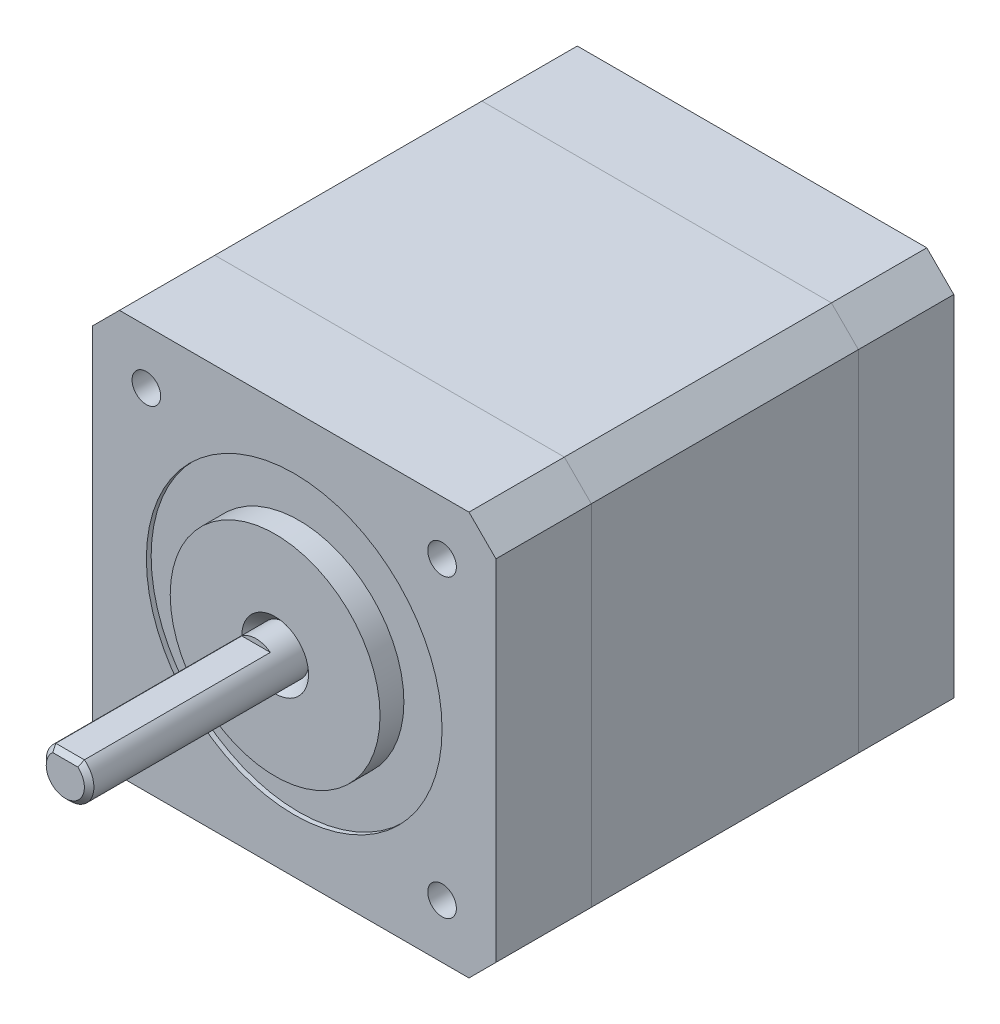
SolidWorks part; units mm, degrees
ref_plane "前视基准面" through (0, 0, 0) normal (0, 0, 1) x (1, 0, 0)
ref_plane "上视基准面" through (0, 0, 0) normal (0, 1, 0) x (1, 0, 0)
ref_plane "右视基准面" through (0, 0, 0) normal (1, 0, 0) x (0, 0, -1)
sketch "草图1" plane through (0, 0, 0) normal (0, 0, 1) x (1, 0, 0)
  line L0 (0, -21.15) -> (0, 21.15) construction
  line L1 (18.3216, 21.15) -> (-18.3216, 21.15)
  line L2 (-18.3216, 21.15) -> (-21.15, 18.3216)
  line L3 (-21.15, 18.3216) -> (-21.15, -18.3216)
  line L4 (-21.15, -18.3216) -> (-18.3216, -21.15)
  line L5 (-18.3216, -21.15) -> (18.3216, -21.15)
  line L6 (21.15, -18.3216) -> (18.3216, -21.15)
  line L7 (18.3216, 21.15) -> (21.15, 18.3216)
  line L8 (21.15, 18.3216) -> (21.15, -18.3216)
  line L9 (-19.7358, 19.7358) -> (0, 0) construction
  line L10 (-15.5, 15.5) -> (15.5, 15.5) construction
  circle A0 centre (-15.5, 15.5) radius 1.5
  circle A1 centre (15.5, 15.5) radius 1.5
  circle A2 centre (15.5, -15.5) radius 1.5
  circle A3 centre (-15.5, -15.5) radius 1.5
  circle A4 centre (0, 0) radius 15.5
  circle A6 centre (0, 0) radius 11
  circle A8 centre (0, 0) radius 2.5
  dimension "D5" = 3
  dimension "D8" = 5
  dimension "D9" = 22
  dimension "D1" = 135
  dimension "D2" = 42.3
  dimension "D3" = 42.3
  dimension "D4" = 4
  dimension "D6" = 31
  dimension "D7" = 4
extrude "凸台-拉伸1" add sketch "草图1" against normal blind 10 contours L8 L7 L1 L2 L3 L4 L5 L6 A4 A3 A2 A1 A0 | A4 | A6 | A6 | A8 | A8 region at (19.3128, 19.3128, 0) region at (-15.0616, 0, 0) region at (-10.6889, 0, 0) region at (0, 0, 0)
sketch "草图2" plane through (0, 0, -10) normal (0, 0, -1) x (-1, 0, 0)
  line L8 (-21.15, 18.3216) -> (-21.15, -18.3216)
  line L9 (-21.15, -18.3216) -> (-18.3216, -21.15)
  line L10 (-18.3216, -21.15) -> (18.3216, -21.15)
  line L11 (18.3216, -21.15) -> (21.15, -18.3216)
  line L12 (21.15, -18.3216) -> (21.15, 18.3216)
  line L13 (21.15, 18.3216) -> (18.3216, 21.15)
  line L14 (18.3216, 21.15) -> (-18.3216, 21.15)
  line L15 (-18.3216, 21.15) -> (-21.15, 18.3216)
  line L16 (-21.15, 18.3216) -> (-21.15, -18.3216)
  line L17 (-21.15, -18.3216) -> (-18.3216, -21.15)
  line L18 (-18.3216, -21.15) -> (18.3216, -21.15)
  line L19 (18.3216, -21.15) -> (21.15, -18.3216)
  line L20 (21.15, -18.3216) -> (21.15, 18.3216)
  line L21 (21.15, 18.3216) -> (18.3216, 21.15)
  line L22 (18.3216, 21.15) -> (-18.3216, 21.15)
  line L23 (-18.3216, 21.15) -> (-21.15, 18.3216)
  dimension "D1" = 0
extrude "凸台-拉伸2" add sketch "草图2" along normal blind 28 separate body
sketch "草图3" plane through (0, 0, -38) normal (0, 0, -1) x (-1, 0, 0)
  line L8 (-18.3216, 21.15) -> (-21.15, 18.3216)
  line L9 (-21.15, 18.3216) -> (-21.15, -18.3216)
  line L10 (-21.15, -18.3216) -> (-18.3216, -21.15)
  line L11 (-18.3216, -21.15) -> (18.3216, -21.15)
  line L12 (18.3216, -21.15) -> (21.15, -18.3216)
  line L13 (21.15, -18.3216) -> (21.15, 18.3216)
  line L14 (21.15, 18.3216) -> (18.3216, 21.15)
  line L15 (18.3216, 21.15) -> (-18.3216, 21.15)
  line L16 (-18.3216, 21.15) -> (-21.15, 18.3216)
  line L17 (-21.15, 18.3216) -> (-21.15, -18.3216)
  line L18 (-21.15, -18.3216) -> (-18.3216, -21.15)
  line L19 (-18.3216, -21.15) -> (18.3216, -21.15)
  line L20 (18.3216, -21.15) -> (21.15, -18.3216)
  line L21 (21.15, -18.3216) -> (21.15, 18.3216)
  line L22 (21.15, 18.3216) -> (18.3216, 21.15)
  line L23 (18.3216, 21.15) -> (-18.3216, 21.15)
  dimension "D1" = 0
extrude "凸台-拉伸3" add sketch "草图3" along normal blind 10 separate body
extrude "切除-拉伸1" cut sketch "草图1<3>" against normal blind 0.5 contours A4 region at (-15.0616, 0, 0)
sketch "草图1<3>" plane through (0, 0, 0) normal (0, 0, 1) x (1, 0, 0) same geometry as "草图1"
extrude "凸台-拉伸4" add sketch "草图1<4>" along normal blind 2 contours A6 region at (-10.6889, 0, 0)
sketch "草图1<4>" plane through (0, 0, 0) normal (0, 0, 1) x (1, 0, 0) same geometry as "草图1"
chamfer "倒角1" distance 1 1 edges at (2.5, 0, 2)
extrude "凸台-拉伸5" add sketch "草图1<5>" along normal blind 24 separate body contours A8 region at (0, 0, 0)
sketch "草图1<5>" plane through (0, 0, 0) normal (0, 0, 1) x (1, 0, 0) same geometry as "草图1"
sketch "草图4" plane through (0, 0, 24) normal (0, 0, 1) x (1, 0, 0)
  line L0 (-1.5, 2) -> (1.5, 2)
  circle A1 centre (0, 0) radius 2.5
  arc A2 (1.5, 2) -> (-1.5, 2) centre (0, 0) ccw
  dimension "D2" = 0.5
  dimension "D1" = 0
extrude "切除-拉伸2" cut sketch "草图4" against normal blind 20
chamfer "倒角2" distance 0.5 2 edges at (0, 2, 24) (0, -2.5, 24)
sketch "草图5" plane through (0, 0, 24) normal (0, 0, 1) x (1, 0, 0)
  circle A0 centre (0, 0) radius 38.5
  point P3 (-38.5, 0)
  dimension "D1" = 77
